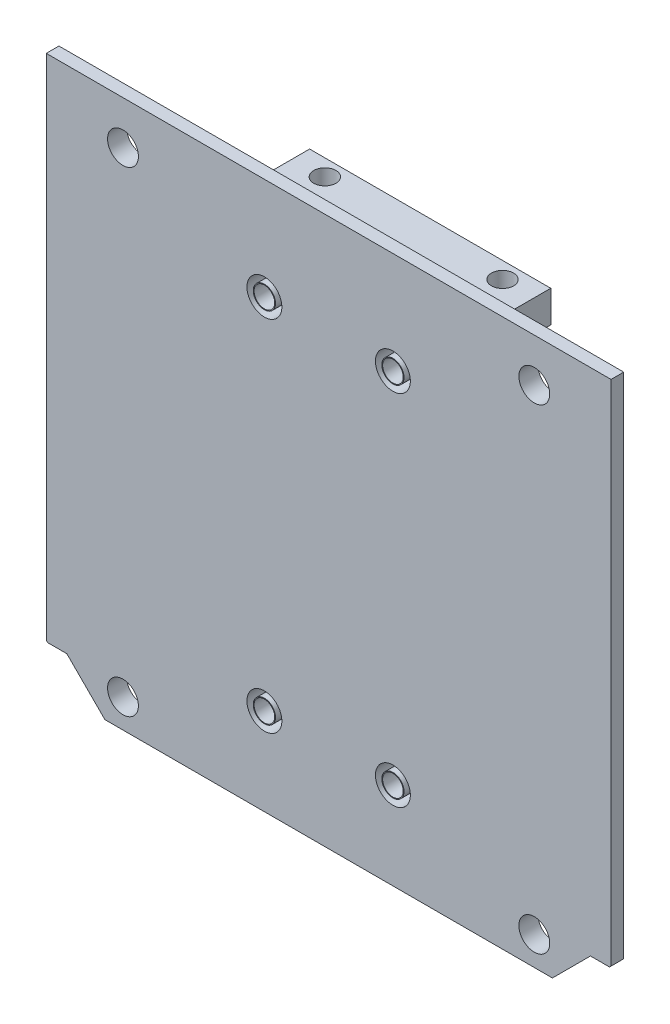
SolidWorks part; units mm, degrees
ref_plane "Front Plane" through (0, 0, 0) normal (0, 0, 1) x (1, 0, 0)
ref_plane "Top Plane" through (0, 0, 0) normal (0, 1, 0) x (1, 0, 0)
ref_plane "Right Plane" through (0, 0, 0) normal (1, 0, 0) x (0, 0, -1)
sketch "Sketch3" plane through (0, 0, 0) normal (0, 0, 1) x (1, 0, 0)
  line L5 (127.5, 163.8458) -> (177.5, 163.8458) construction
  line L6 (127.5, 163.8458) -> (127.5, 113.8458) construction
  line L7 (127.5, 113.8458) -> (177.5, 113.8458) construction
  line L8 (177.5, 163.8458) -> (177.5, 113.8458) construction
  line L9 (127.5, 163.8458) -> (177.5, 113.8458) construction
  line L10 (127.5, 113.8458) -> (177.5, 163.8458) construction
  line L12 (121.5, 169.8458) -> (183.5, 169.8458) construction
  line L13 (121.5, 169.8458) -> (121.5, 107.8458) construction
  line L14 (121.5, 107.8458) -> (183.5, 107.8458) construction
  line L15 (183.5, 169.8458) -> (183.5, 107.8458) construction
  line L16 (121.5, 169.8458) -> (183.5, 107.8458) construction
  line L17 (121.5, 107.8458) -> (183.5, 169.8458) construction
  line L21 (171.5, 107.8458) -> (133.5, 107.8458)
  line L22 (171.5, 113.8458) -> (171.5, 107.8458)
  line L23 (171.5, 113.8458) -> (133.5, 113.8458)
  line L24 (133.5, 107.8458) -> (133.5, 113.8458)
  line L29 (133.5, 169.8458) -> (171.5, 169.8458)
  line L30 (133.5, 163.8458) -> (133.5, 169.8458)
  line L31 (133.5, 163.8458) -> (171.5, 163.8458)
  line L32 (171.5, 169.8458) -> (171.5, 163.8458)
  point P0 (152.5, 138.8458)
  point P7 (152.5, 138.8458)
  point P15 (177.5, 138.8458)
  point P32 (152.5, 138.8458)
extrude "Boss-Extrude2" add sketch "Sketch3" against normal blind 8
sketch "Sketch1" plane through (0, 0, 0) normal (0, 0, 1) x (1, 0, 0)
  line L5 (199, 102.26) -> (199, 185.1542) construction
  line L6 (199, 185.1542) -> (106, 185.1542) construction
  line L8 (106, 185.1542) -> (106, 102.26) construction
  line L11 (106, 102.26) -> (107.4142, 100.8458) construction
  line L12 (107.4142, 100.8458) -> (110.4142, 100.8458) construction
  line L13 (110.4142, 100.8458) -> (116.4142, 94.8458) construction
  line L14 (116.4142, 94.8458) -> (188.5858, 94.8458) construction
  line L15 (188.5858, 94.8458) -> (194.5858, 100.8458) construction
  line L16 (194.5858, 100.8458) -> (197.5858, 100.8458) construction
  line L17 (197.5858, 100.8458) -> (199, 102.26) construction
  line L18 (197, 103.0884) -> (197, 183.1542)
  line L19 (197, 183.1542) -> (108, 183.1542)
  line L20 (108, 183.1542) -> (108, 103.0885)
  line L21 (108, 103.0885) -> (108.2426, 102.8458)
  line L22 (108.2426, 102.8458) -> (111.2426, 102.8458)
  line L23 (111.2426, 102.8458) -> (117.2426, 96.8458)
  line L24 (117.2426, 96.8458) -> (187.7574, 96.8458)
  line L25 (187.7574, 96.8458) -> (193.7574, 102.8458)
  line L26 (193.7574, 102.8458) -> (196.7574, 102.8458)
  line L27 (196.7574, 102.8458) -> (197, 103.0884)
  circle A0 centre (184.9067, 176.3226) radius 2.43
  circle A1 centre (120.09, 176.3226) radius 2.43
  circle A2 centre (184.9067, 101.3711) radius 2.43
  circle A3 centre (120.09, 101.3711) radius 2.43
  point P0 (152.5, 138.8458)
  point P14 (152.5, 138.8458)
  dimension "D1" = 2
extrude "Boss-Extrude3" add sketch "Sketch1" against normal blind 3
chamfer "Chamfer1" distance 1 angle 45 8 edges at (109.7426, 102.8458, -3) (114.2426, 99.8458, -3) (195.2574, 102.8458, -3) (190.7574, 99.8458, -3) (152.5, 96.8458, -3) (108, 143.1213, -3) (152.5, 183.1542, -3) (197, 143.1213, -3)
sketch "Sketch4" plane through (0, 0, 0) normal (0, 0, 1) x (1, 0, 0)
  line L0 (171.5, 169.8458) -> (133.5, 169.8458)
  line L1 (171.5, 169.8458) -> (171.5, 174.8458)
  line L2 (133.5, 169.8458) -> (133.5, 174.8458)
  line L3 (171.5, 174.8458) -> (133.5, 174.8458)
  line L4 (171.5, 107.8458) -> (133.5, 107.8458)
  line L5 (171.5, 107.8458) -> (171.5, 102.8458)
  line L6 (133.5, 107.8458) -> (133.5, 102.8458)
  line L7 (171.5, 102.8458) -> (133.5, 102.8458)
  dimension "D1" = 5
  dimension "D2" = 5
extrude "Boss-Extrude4" add sketch "Sketch4" against normal blind 16
sketch "Sketch5" plane through (0, 102.8458, 0) normal (0, -1, 0) x (-1, 0, 0)
  line L0 (-171.5, 13.4) -> (-133.5, 13.4) construction
  line L5 (-171.5, 16) -> (-171.5, 3) construction
  line L6 (-133.5, 16) -> (-133.5, 3) construction
  line L8 (-136.75, 15.15) -> (-168.25, 15.15) construction
  line L9 (-136.75, 15.15) -> (-136.75, 11.65) construction
  line L10 (-136.75, 11.65) -> (-168.25, 11.65) construction
  line L11 (-168.25, 15.15) -> (-168.25, 11.65) construction
  line L12 (-136.75, 15.15) -> (-168.25, 11.65) construction
  line L13 (-136.75, 11.65) -> (-168.25, 15.15) construction
  line L14 (-140, 17.6971) -> (-165, 17.6971) construction
  line L15 (-140, 17.6971) -> (-140, 9.1029) construction
  line L16 (-140, 9.1029) -> (-165, 9.1029) construction
  line L17 (-165, 17.6971) -> (-165, 9.1029) construction
  line L18 (-140, 17.6971) -> (-165, 9.1029) construction
  line L19 (-140, 9.1029) -> (-165, 17.6971) construction
  line L21 (-171.5, 3) -> (-133.5, 3) construction
  circle A0 centre (-166.5, 13.4) radius 1.75
  circle A1 centre (-138.5, 13.4) radius 1.75
  point P0 (-152.5, 13.4)
  point P17 (-152.5, 13.4)
  dimension "D2" = 3.5
  dimension "D4" = 3.5
  dimension "D5" = 8.65
  dimension "D1" = 28
  dimension "D3" = 25
extrude "Cut-Extrude1" cut sketch "Sketch5" against normal blind 80
sketch "Sketch6" plane through (0, 0, -8) normal (0, 0, -1) x (-1, 0, 0)
  line L0 (-171.5, 167.0958) -> (-133.5, 167.0958) construction
  line L1 (-171.5, 169.8458) -> (-171.5, 163.8458) construction
  line L2 (-133.5, 163.8458) -> (-133.5, 169.8458) construction
  line L3 (-171.5, 110.5958) -> (-133.5, 110.5958) construction
  line L4 (-140.75, 165.3458) -> (-164.25, 165.3458) construction
  line L5 (-140.75, 165.3458) -> (-140.75, 168.8458) construction
  line L6 (-140.75, 168.8458) -> (-164.25, 168.8458) construction
  line L7 (-164.25, 165.3458) -> (-164.25, 168.8458) construction
  line L8 (-140.75, 165.3458) -> (-164.25, 168.8458) construction
  line L9 (-140.75, 168.8458) -> (-164.25, 165.3458) construction
  line L10 (-171.5, 113.8458) -> (-171.5, 107.8458) construction
  line L11 (-133.5, 107.8458) -> (-133.5, 113.8458) construction
  line L12 (-171.5, 108.8458) -> (-133.5, 108.8458)
  line L13 (-140.75, 108.8458) -> (-164.25, 108.8458) construction
  line L14 (-140.75, 108.8458) -> (-140.75, 112.3458) construction
  line L15 (-140.75, 112.3458) -> (-164.25, 112.3458) construction
  line L16 (-164.25, 108.8458) -> (-164.25, 112.3458) construction
  line L17 (-140.75, 108.8458) -> (-164.25, 112.3458) construction
  line L18 (-140.75, 112.3458) -> (-164.25, 108.8458) construction
  line L19 (-171.5, 107.8458) -> (-133.5, 107.8458) construction
  circle A0 centre (-162.625, 167.0958) radius 1.625
  circle A1 centre (-142.375, 167.0958) radius 1.625
  circle A2 centre (-162.625, 110.5958) radius 1.625
  circle A3 centre (-142.375, 110.5958) radius 1.625
  point P6 (-152.5, 167.0958)
  point P21 (-152.5, 110.5958)
  dimension "D4" = 56.5
  dimension "D1" = 23.5
  dimension "D5" = 1
  dimension "D6" = 3.5
  dimension "D7" = 3.5
extrude "Cut-Extrude2" cut sketch "Sketch6" against normal blind 10 contours A2 | A3 | A0 | A1 region at (162.625, 167.0958, -8) region at (142.375, 167.0958, -8) region at (162.625, 110.5958, -8) region at (142.375, 110.5958, -8)
sketch "Sketch7" plane through (0, 0, 0) normal (0, 0, 1) x (1, 0, 0)
  circle A0 centre (162.625, 167.0958) radius 1.75
  circle A1 centre (162.625, 167.0958) radius 2.75
  circle A2 centre (142.375, 167.0958) radius 1.75
  circle A3 centre (142.375, 167.0958) radius 2.75
  circle A4 centre (162.625, 110.5958) radius 1.75
  circle A5 centre (162.625, 110.5958) radius 2.75
  circle A6 centre (142.375, 110.5958) radius 1.75
  circle A7 centre (142.375, 110.5958) radius 2.75
extrude "Cut-Extrude3" cut sketch "Sketch7" against normal blind 4
